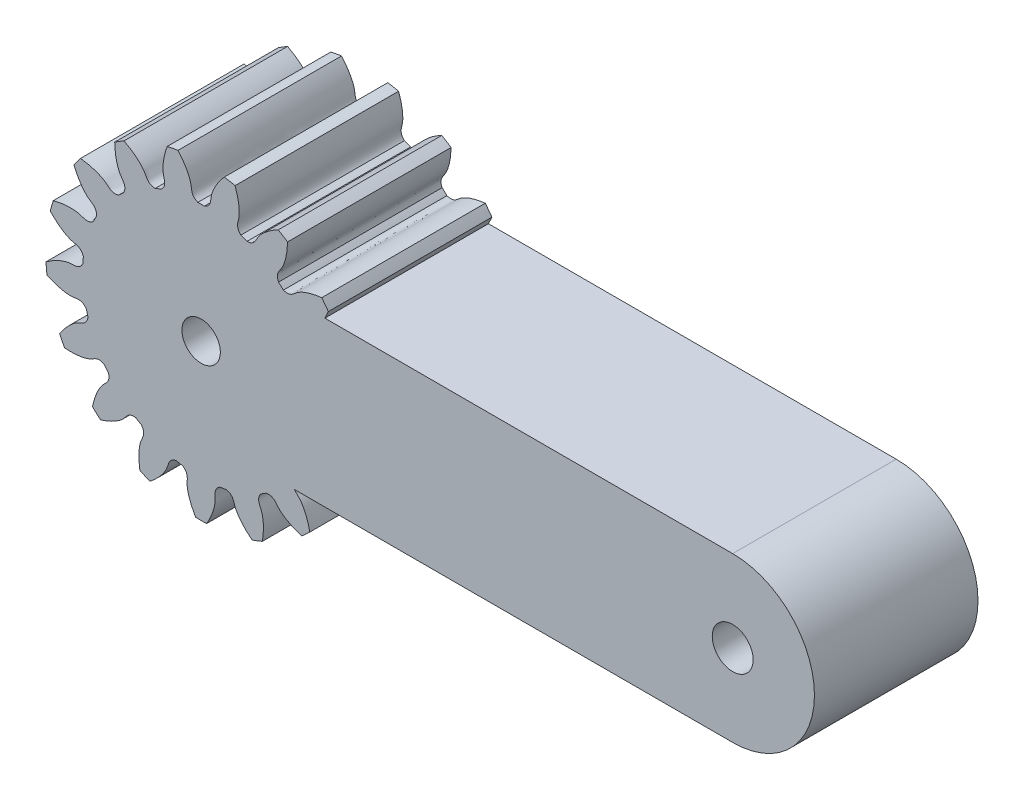
SolidWorks part; units mm, degrees
ref_plane "前视基准面" through (0, 0, 0) normal (0, 0, 1) x (1, 0, 0)
ref_plane "上视基准面" through (0, 0, 0) normal (0, 1, 0) x (1, 0, 0)
ref_plane "右视基准面" through (0, 0, 0) normal (1, 0, 0) x (0, 0, -1)
sketch "草图1" plane through (0, 0, 0) normal (0, 0, 1) x (1, 0, 0)
  circle A0 centre (0, 0) radius 19
extrude "凸台-拉伸1" add sketch "草图1" along normal blind 20
ref_axis "基准轴1" through (0, 0, -1.5) along (0, 0, 1)
sketch "草图2" plane through (0, 0, 0) normal (0, 0, 1) x (1, 0, 0)
  line L0 (0, 0) -> (0, 19) construction
  circle A0 centre (0, 0) radius 19 construction
  arc A1 (0.4034, 14.4944) -> (-0.4034, 14.4944) centre (0, 0) ccw
  arc A2 (6.2313, 21.4814) -> (-6.2313, 21.4814) centre (0, 0) ccw
  spline S0 degree 3 poles (0.4034, 14.4944) (1.2558, 14.8496) (1.1324, 15.5096) (1.2766, 16.1296) (1.29, 16.1823) (1.306, 16.2408) (1.3251, 16.3052) (1.3474, 16.3752) (1.3731, 16.4508) (1.4025, 16.5319) (1.4359, 16.6184) (1.4733, 16.7101) (1.5152, 16.8068) (1.5616, 16.9086) (1.6128, 17.0151) (1.669, 17.1264) (1.7304, 17.2421) (1.7972, 17.3621) (1.8696, 17.4863) (1.9478, 17.6145) (2.032, 17.7465) (2.1224, 17.8821) (2.2191, 18.0211) (2.3223, 18.1634) (2.4322, 18.3086) (2.5489, 18.4566) (2.6727, 18.6072) (2.8035, 18.7601) (2.9417, 18.9152) (3.0873, 19.0722) (3.2404, 19.2308) (3.4012, 19.3908) (3.5698, 19.552) (3.7462, 19.7141) (3.9307, 19.8769) (4.1233, 20.0401) (4.324, 20.2035) (4.533, 20.3667) (4.7503, 20.5295) (4.9761, 20.6917) (5.2103, 20.853) (5.453, 21.0131) (5.7916, 21.2269) (6.0532, 21.3811) (6.2313, 21.4814) knots 0 0 0 0 0.193883 0.199024 0.204851 0.211363 0.21856 0.226443 0.235011 0.244265 0.254205 0.264829 0.27614 0.288136 0.300817 0.314184 0.328236 0.342973 0.358397 0.374505 0.391299 0.408779 0.426944 0.445795 0.465331 0.485552 0.506459 0.528051 0.550329 0.573293 0.596941 0.621276 0.646296 0.672001 0.698392 0.725468 0.753229 0.781677 0.810809 0.840627 0.871131 0.90232 0.934195 1 1 1 1
  spline S1 degree 3 poles (-0.4034, 14.4944) (-1.2558, 14.8496) (-1.1324, 15.5096) (-1.2766, 16.1296) (-1.29, 16.1823) (-1.306, 16.2408) (-1.3251, 16.3052) (-1.3474, 16.3752) (-1.3731, 16.4508) (-1.4025, 16.5319) (-1.4359, 16.6184) (-1.4733, 16.7101) (-1.5152, 16.8068) (-1.5616, 16.9086) (-1.6128, 17.0151) (-1.669, 17.1264) (-1.7304, 17.2421) (-1.7972, 17.3621) (-1.8696, 17.4863) (-1.9478, 17.6145) (-2.032, 17.7465) (-2.1224, 17.8821) (-2.2191, 18.0211) (-2.3223, 18.1634) (-2.4322, 18.3086) (-2.5489, 18.4566) (-2.6727, 18.6072) (-2.8035, 18.7601) (-2.9417, 18.9152) (-3.0873, 19.0722) (-3.2404, 19.2308) (-3.4012, 19.3908) (-3.5698, 19.552) (-3.7462, 19.7141) (-3.9307, 19.8769) (-4.1233, 20.0401) (-4.324, 20.2035) (-4.533, 20.3667) (-4.7503, 20.5295) (-4.9761, 20.6917) (-5.2103, 20.853) (-5.453, 21.0131) (-5.7916, 21.2269) (-6.0532, 21.3811) (-6.2313, 21.4814) knots 0 0 0 0 0.193883 0.199024 0.204851 0.211363 0.21856 0.226443 0.235011 0.244265 0.254205 0.264829 0.27614 0.288136 0.300817 0.314184 0.328236 0.342973 0.358397 0.374505 0.391299 0.408779 0.426944 0.445795 0.465331 0.485552 0.506459 0.528051 0.550329 0.573293 0.596941 0.621276 0.646296 0.672001 0.698392 0.725468 0.753229 0.781677 0.810809 0.840627 0.871131 0.90232 0.934195 1 1 1 1
extrude "切除-拉伸1" cut sketch "草图2" along normal through all
pattern_circular "阵列(圆周)1" count 17 every 21.176 about axis through (0, 0, -1.5) along (0, 0, 1) of "切除-拉伸1"
sketch "草图3" plane through (0, 0, 0) normal (0, 0, 1) x (1, 0, 0)
  circle A0 centre (0, 0) radius 17 construction
  dimension "Dn" = 34
sketch "草图4" plane through (0, 0, 20) normal (0, 0, 1) x (1, 0, 0)
  line L0 (0, 10) -> (65, 10)
  line L1 (0, -10) -> (65, -10)
  arc A1 (0, -10) -> (0, 10) centre (0, 0) cw
  arc A2 (65, 10) -> (65, -10) centre (65, 0) cw
  dimension "D1" = 10
  dimension "D2" = 65
extrude "凸台-拉伸2" add sketch "草图4" against normal blind 20
sketch "草图5" plane through (0, 0, 0) normal (0, 0, -1) x (-1, 0, 0)
  line L0 (-65, 10) -> (-65, -15.2888) construction
  line L1 (-75, 0) -> (23.6959, 0) construction
  circle A0 centre (0, 0) radius 2.3479
  arc A1 (-65, 10) -> (-65, -10) centre (-65, 0) ccw construction
  circle A2 centre (-65, 0) radius 2.5
  dimension "D1" = 5
extrude "切除-拉伸2" cut sketch "草图5" against normal blind 20
